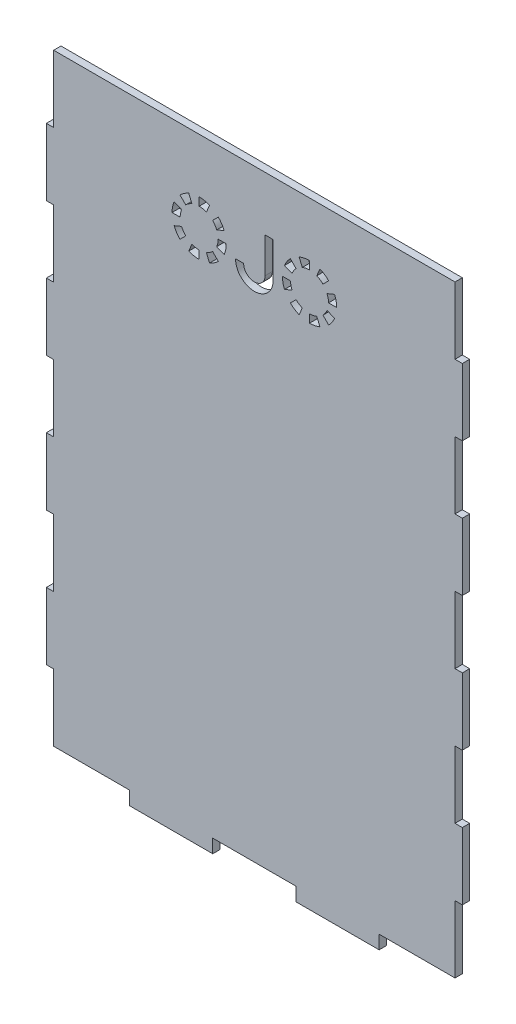
SolidWorks part; units mm, degrees
ref_plane "Ön Düzlem" through (0, 0, 0) normal (0, 0, 1) x (1, 0, 0)
ref_plane "Üst Düzlem" through (0, 0, 0) normal (0, 1, 0) x (1, 0, 0)
ref_plane "Sağ Düzlem" through (0, 0, 0) normal (1, 0, 0) x (0, 0, -1)
sketch "Sketch1" plane through (0, 0, 0) normal (0, 0, 1) x (1, 0, 0)
  line L0 (46.02, -108.65) -> (74, -108.65)
  line L3 (74, 113.65) -> (-74, 113.65)
  line L5 (73.3256, -108.65) -> (-74, 109.6493) construction
  line L6 (74, 109.6493) -> (-73.3256, -108.65) construction
  line L7 (-74, -108.65) -> (-46.02, -108.65)
  line L8 (-15.34, -108.65) -> (15.34, -108.65)
  line L9 (-74, -108.65) -> (-74, -83.95)
  line L11 (74, -108.65) -> (74, -83.95)
  line L13 (-74, -59.25) -> (-74, -34.55)
  line L15 (-74, -9.85) -> (-74, 14.85)
  line L16 (-76.7, 14.85) -> (-76.7, 39.55)
  line L17 (-74, 39.55) -> (-74, 64.25)
  line L18 (-76.7, -34.55) -> (-76.7, -9.85)
  line L19 (-74, 88.95) -> (-74, 113.65)
  line L20 (76.7, -34.55) -> (76.7, -9.85)
  line L21 (74, -59.25) -> (74, -34.55)
  line L22 (76.7, 14.85) -> (76.7, 39.55)
  line L23 (74, -9.85) -> (74, 14.85)
  line L24 (76.7, 64.25) -> (76.7, 88.95)
  line L25 (74, 39.55) -> (74, 64.25)
  line L26 (46.02, -113.65) -> (15.34, -113.65)
  line L27 (74, 88.95) -> (74, 113.65)
  line L28 (-74, 88.95) -> (-76.7, 88.95)
  line L29 (-74, 64.25) -> (-76.7, 64.25)
  line L30 (-74, 39.55) -> (-76.7, 39.55)
  line L31 (-74, 14.85) -> (-76.7, 14.85)
  line L32 (-74, -9.85) -> (-76.7, -9.85)
  line L33 (-74, -34.55) -> (-76.7, -34.55)
  line L34 (-74, -83.95) -> (-76.7, -83.95)
  line L35 (74, -83.95) -> (76.7, -83.95)
  line L36 (74, 88.95) -> (76.7, 88.95)
  line L37 (74, 64.25) -> (76.7, 64.25)
  line L38 (74, 39.55) -> (76.7, 39.55)
  line L39 (74, 14.85) -> (76.7, 14.85)
  line L40 (74, -9.85) -> (76.7, -9.85)
  line L41 (74, -34.55) -> (76.7, -34.55)
  line L42 (74, -59.25) -> (76.7, -59.25)
  line L43 (-76.7, 64.25) -> (-76.7, 88.95)
  line L44 (-76.7, -83.95) -> (-76.7, -61.75)
  line L45 (76.7, -83.95) -> (76.7, -59.25)
  line L46 (-74, -59.25) -> (-76.7, -59.25)
  line L47 (-15.34, -113.65) -> (-46.02, -113.65)
  line L48 (-76.7, -61.75) -> (-76.7, -59.25)
  line L49 (-46.02, -113.65) -> (-46.02, -108.65)
  line L50 (-15.34, -113.65) -> (-15.34, -108.65)
  line L51 (15.34, -113.65) -> (15.34, -108.65)
  line L52 (46.02, -113.65) -> (46.02, -108.65)
  line L63 (-13.2808, 76.5789) -> (-15.4021, 78.7003)
  line L64 (-11.113, 79.8232) -> (-13.8847, 80.9712)
  line L65 (-10.3518, 83.65) -> (-13.3518, 83.65)
  line L66 (-11.113, 87.4768) -> (-13.8847, 86.3288)
  line L67 (-13.2808, 90.7211) -> (-15.4021, 88.5997)
  line L68 (-16.525, 92.8888) -> (-17.673, 90.1172)
  line L69 (-20.3518, 93.65) -> (-20.3518, 90.65)
  line L70 (-23.0306, 90.1172) -> (-24.1787, 92.8888)
  line L71 (-25.3016, 88.5997) -> (-27.4229, 90.7211)
  line L72 (-26.819, 86.3288) -> (-29.5906, 87.4768)
  line L73 (-27.3518, 83.65) -> (-30.3518, 83.65)
  line L74 (-26.819, 80.9712) -> (-29.5906, 79.8232)
  line L75 (-25.3016, 78.7003) -> (-27.4229, 76.5789)
  line L76 (-23.0306, 77.1828) -> (-24.1787, 74.4112)
  line L77 (-20.3518, 76.65) -> (-20.3518, 73.65)
  line L78 (-16.525, 74.4112) -> (-17.673, 77.1828)
  line L79 (23.0306, 77.1828) -> (24.1787, 74.4112)
  line L80 (20.3518, 76.65) -> (20.3518, 73.65)
  line L81 (26.819, 80.9712) -> (29.5906, 79.8232)
  line L82 (25.3016, 78.7003) -> (27.4229, 76.5789)
  line L83 (26.819, 86.3288) -> (29.5906, 87.4768)
  line L84 (27.3518, 83.65) -> (30.3518, 83.65)
  line L85 (23.0306, 90.1172) -> (24.1787, 92.8888)
  line L86 (25.3016, 88.5997) -> (27.4229, 90.7211)
  line L87 (16.525, 92.8888) -> (17.673, 90.1172)
  line L88 (20.3518, 93.65) -> (20.3518, 90.65)
  line L89 (11.113, 87.4768) -> (13.8847, 86.3288)
  line L90 (13.2808, 90.7211) -> (15.4021, 88.5997)
  line L91 (11.113, 79.8232) -> (13.8847, 80.9712)
  line L92 (10.3518, 83.65) -> (13.3518, 83.65)
  line L93 (13.2808, 76.5789) -> (15.4021, 78.7003)
  line L94 (16.525, 74.4112) -> (17.673, 77.1828)
  line L98 (-6.9421, 80.5931) -> (-3.939, 80.5931)
  line L100 (6.944, 93.65) -> (3.9304, 93.65)
  line L101 (3.941, 80.5931) -> (3.9304, 93.65)
  line L102 (6.944, 80.5931) -> (6.944, 93.65)
  arc A0 (-11.113, 87.4768) -> (-13.2808, 90.7211) centre (-20.3518, 83.65) ccw
  arc A3 (-23.0306, 90.1172) -> (-25.3016, 88.5997) centre (-20.3518, 83.65) ccw
  arc A5 (-16.525, 92.8888) -> (-20.3518, 93.65) centre (-20.3518, 83.65) ccw
  arc A7 (-24.1787, 92.8888) -> (-27.4229, 90.7211) centre (-20.3518, 83.65) ccw
  arc A9 (-29.5906, 87.4768) -> (-30.3518, 83.65) centre (-20.3518, 83.65) ccw
  arc A11 (-29.5906, 79.8232) -> (-27.4229, 76.5789) centre (-20.3518, 83.65) ccw
  arc A13 (-24.1787, 74.4112) -> (-20.3518, 73.65) centre (-20.3518, 83.65) ccw
  arc A15 (-16.525, 74.4112) -> (-13.2808, 76.5789) centre (-20.3518, 83.65) ccw
  arc A17 (-11.113, 79.8232) -> (-10.3518, 83.65) centre (-20.3518, 83.65) ccw
  arc A19 (-17.673, 90.1172) -> (-20.3518, 90.65) centre (-20.3518, 83.65) ccw
  arc A20 (-13.8847, 86.3288) -> (-15.4021, 88.5997) centre (-20.3518, 83.65) ccw
  arc A21 (-13.8847, 80.9712) -> (-13.3518, 83.65) centre (-20.3518, 83.65) ccw
  arc A22 (-17.673, 77.1828) -> (-15.4021, 78.7003) centre (-20.3518, 83.65) ccw
  arc A23 (-23.0306, 77.1828) -> (-20.3518, 76.65) centre (-20.3518, 83.65) ccw
  arc A24 (-26.819, 80.9712) -> (-25.3016, 78.7003) centre (-20.3518, 83.65) ccw
  arc A25 (-26.819, 86.3288) -> (-27.3518, 83.65) centre (-20.3518, 83.65) ccw
  arc A26 (23.0306, 77.1828) -> (20.3518, 76.65) centre (20.3518, 83.65) cw
  arc A27 (24.1787, 74.4112) -> (20.3518, 73.65) centre (20.3518, 83.65) cw
  arc A28 (26.819, 80.9712) -> (25.3016, 78.7003) centre (20.3518, 83.65) cw
  arc A29 (29.5906, 79.8232) -> (27.4229, 76.5789) centre (20.3518, 83.65) cw
  arc A30 (26.819, 86.3288) -> (27.3518, 83.65) centre (20.3518, 83.65) cw
  arc A31 (29.5906, 87.4768) -> (30.3518, 83.65) centre (20.3518, 83.65) cw
  arc A32 (23.0306, 90.1172) -> (25.3016, 88.5997) centre (20.3518, 83.65) cw
  arc A33 (24.1787, 92.8888) -> (27.4229, 90.7211) centre (20.3518, 83.65) cw
  arc A34 (16.525, 92.8888) -> (20.3518, 93.65) centre (20.3518, 83.65) cw
  arc A35 (17.673, 90.1172) -> (20.3518, 90.65) centre (20.3518, 83.65) cw
  arc A36 (11.113, 87.4768) -> (13.2808, 90.7211) centre (20.3518, 83.65) cw
  arc A37 (13.8847, 86.3288) -> (15.4021, 88.5997) centre (20.3518, 83.65) cw
  arc A38 (11.113, 79.8232) -> (10.3518, 83.65) centre (20.3518, 83.65) cw
  arc A39 (13.8847, 80.9712) -> (13.3518, 83.65) centre (20.3518, 83.65) cw
  arc A40 (16.525, 74.4112) -> (13.2808, 76.5789) centre (20.3518, 83.65) cw
  arc A41 (17.673, 77.1828) -> (15.4021, 78.7003) centre (20.3518, 83.65) cw
  arc A43 (-6.9421, 80.5931) -> (6.944, 80.5931) centre (0.001, 80.5931) ccw
  arc A44 (-3.939, 80.5931) -> (3.941, 80.5931) centre (0.001, 80.5931) ccw
  point P0 (0, 0)
extrude "Boss-Extrude2" add sketch "Sketch1" along normal blind 2.7
